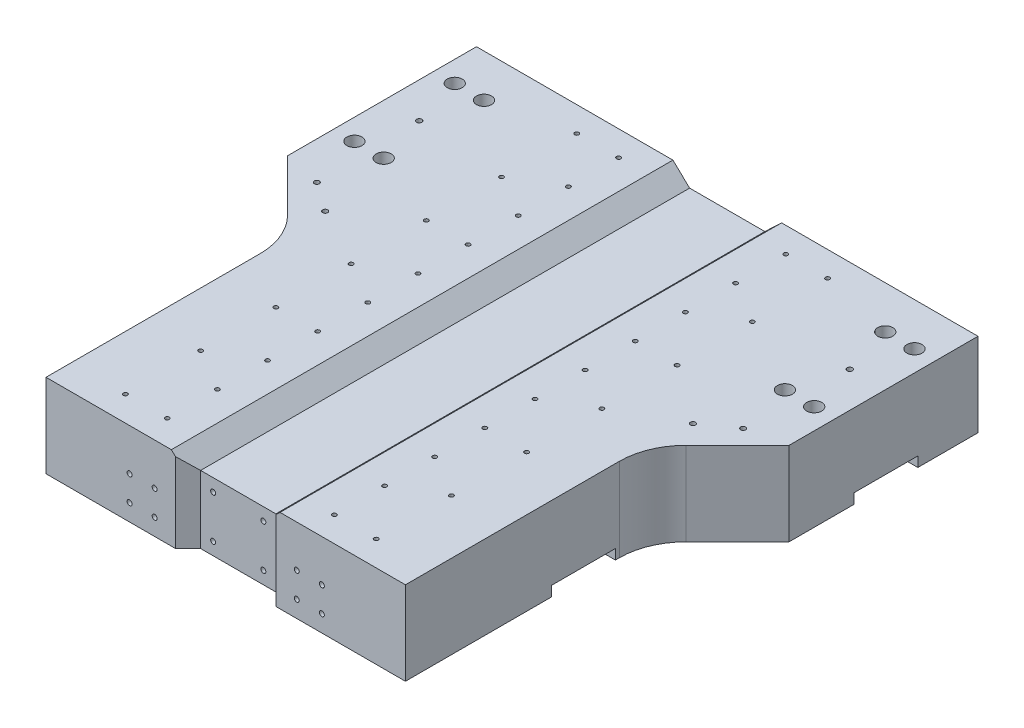
SolidWorks part; units mm, degrees
ref_plane "Front Plane" through (0, 0, 0) normal (0, 0, 1) x (1, 0, 0)
ref_plane "Top Plane" through (0, 0, 0) normal (0, 1, 0) x (1, 0, 0)
ref_plane "Right Plane" through (0, 0, 0) normal (1, 0, 0) x (0, 0, -1)
sketch "Sketch1" plane through (0, 0, 0) normal (0, 1, 0) x (1, 0, 0)
  line L1 (-300, 300) -> (300, 300)
  line L2 (-300, 300) -> (-300, -300)
  line L3 (-300, -300) -> (300, -300)
  line L4 (300, 300) -> (300, -300)
  line L5 (0, -300) -> (0, 300) construction
  line L6 (-300, 0) -> (300, 0) construction
  point P0 (0, 0)
  dimension "D1" = 600
extrude "Boss-Extrude1" add sketch "Sketch1" along normal blind 100
sketch "Sketch2" plane through (0, 100, 0) normal (0, 1, 0) x (1, 0, 0)
  line L0 (-300, -300) -> (-220, -300)
  line L9 (-300, -300) -> (300, -300) construction
  line L11 (300, -300) -> (220, -300)
  line L13 (-300, 300) -> (-300, -300) construction
  line L15 (-300, -300) -> (-300, 60)
  line L16 (300, -300) -> (300, 60)
  line L38 (-300, 60) -> (-300, 74)
  line L41 (300, 60) -> (300, 74)
  line L45 (-220, 74) -> (-300, 74)
  line L48 (220, 74) -> (300, 74)
  line L49 (-220, 74) -> (-215, 74)
  line L50 (-215, 74) -> (-215, -300)
  line L51 (-215, -300) -> (-220, -300)
  line L52 (220, 74) -> (215, 74)
  line L53 (215, 74) -> (215, -300)
  line L54 (215, -300) -> (220, -300)
extrude "Cut-Extrude1" cut sketch "Sketch2" against normal through all
chamfer "Chamfer5" distance 85 angle 45 2 edges at (-215, 50, -74) (215, 50, -74)
sketch "Sketch3" plane through (0, 0, 300) normal (0, 0, 1) x (1, 0, 0)
  line L0 (-35, 81) -> (-45, 81)
  line L2 (35, 81) -> (45, 81)
  line L4 (0, 81) -> (35, 81)
  line L8 (0, 81) -> (-35, 81)
  line L10 (-45, 100) -> (45, 100)
  line L13 (-215, 100) -> (215, 100) construction
  line L14 (-65, 100) -> (-45, 100)
  line L17 (45, 100) -> (65, 100)
  line L22 (-45, 81) -> (-65, 100)
  line L23 (45, 81) -> (65, 100)
extrude "Cut-Extrude2" cut sketch "Sketch3" against normal through all
sketch "Sketch9" plane through (0, 100, 0) normal (0, 1, 0) x (1, 0, 0)
  circle A0 centre (275, 129) radius 9.017
  circle A1 centre (240, 129) radius 9.017
  circle A3 centre (240, 249) radius 9.017
  circle A5 centre (275, 249) radius 9.017
  circle A6 centre (-275, 129) radius 9.017
  circle A7 centre (-240, 249) radius 9.017
  circle A8 centre (-275, 249) radius 9.017
  circle A11 centre (-240, 129) radius 9.017
  circle A12 centre (240, 189) radius 9.017 [skipped]
  circle A13 centre (275, 189) radius 9.017 [skipped]
  dimension "D1" = 2
  dimension "D2" = 3
extrude "Cut-Extrude5" cut sketch "Sketch9" against normal through all
sketch "Sketch12" plane through (0, 100, 0) normal (0, 1, 0) x (1, 0, 0)
  circle A40 centre (-100, -270) radius 2.5
  circle A41 centre (100, -270) radius 2.5
  circle A42 centre (100, -210) radius 2.5
  circle A43 centre (100, -150) radius 2.5
  circle A44 centre (100, -90) radius 2.5
  circle A45 centre (100, -30) radius 2.5
  circle A46 centre (100, 30) radius 2.5
  circle A47 centre (100, 90) radius 2.5
  circle A48 centre (100, 150) radius 2.5
  circle A49 centre (100, 210) radius 2.5
  circle A50 centre (100, 270) radius 2.5
  circle A61 centre (-100, -210) radius 2.5
  circle A62 centre (-100, -150) radius 2.5
  circle A63 centre (-100, -90) radius 2.5
  circle A64 centre (-100, -30) radius 2.5
  circle A65 centre (-100, 30) radius 2.5
  circle A66 centre (-100, 90) radius 2.5
  circle A67 centre (-100, 150) radius 2.5
  circle A68 centre (-100, 210) radius 2.5
  circle A69 centre (-100, 270) radius 2.5
  dimension "D1" = 2
  dimension "D2" = 10
extrude "Cut-Extrude7" cut sketch "Sketch12" against normal blind 30
sketch "Sketch14" plane through (0, 81, 0) normal (0, 1, 0) x (1, 0, 0)
  line L5 (-45, -300) -> (45, -300)
  line L6 (-45, -300) -> (-45, -285)
  line L11 (45, -285) -> (45, -300)
  line L15 (-45, -285) -> (45, -285)
extrude "Cut-Extrude8" cut sketch "Sketch14" against normal through all
chamfer "Chamfer3" distance 15 angle 45 2 edges at (45, 40.5, 300) (-45, 40.5, 300)
sketch "Sketch15" plane through (-300, 0, 0) normal (-1, 0, 0) x (0, 0, 1)
  line L0 (125, -0.7) -> (125, 12) construction
  line L1 (125, 12) -> (48.8, 12) construction
  line L2 (48.8, 12) -> (48.8, -0.7) construction
  line L3 (48.8, -0.7) -> (125, -0.7) construction
  line L4 (-228, 12) -> (-228, -0.7) construction
  line L5 (-228, -0.7) -> (-151.8, -0.7) construction
  line L6 (-151.8, -0.7) -> (-151.8, 12) construction
  line L7 (-151.8, 12) -> (-228, 12) construction
  line L8 (125, -0.7) -> (125, 12)
  line L9 (125, 12) -> (48.8, 12)
  line L10 (48.8, 12) -> (48.8, -0.7)
  line L11 (48.8, -0.7) -> (125, -0.7)
  line L12 (-228, 12) -> (-228, -0.7)
  line L13 (-228, -0.7) -> (-151.8, -0.7)
  line L14 (-151.8, -0.7) -> (-151.8, 12)
  line L15 (-151.8, 12) -> (-228, 12)
extrude "Cut-Extrude9" cut sketch "Sketch15" against normal through all
sketch "Sketch22" plane through (0, 0, -300) normal (0, 0, -1) x (-1, 0, 0)
  line L0 (-45, 81) -> (-45, 0)
  line L1 (-300, 0) -> (300, 0) construction
  line L2 (-45, 0) -> (45, 0)
  line L3 (45, 0) -> (45, 81)
  line L4 (45, 81) -> (-45, 81)
sketch "Sketch17" plane through (0, 0, 285) normal (0, 0, 1) x (1, 0, 0)
  line L8 (30, 66) -> (-30, 66)
  line L9 (-30, 66) -> (-30, 15)
  line L10 (-30, 15) -> (30, 15)
  line L11 (30, 15) -> (30, 66)
  line L12 (30, 66) -> (-30, 66)
  line L13 (-30, 66) -> (-30, 15)
  line L14 (-30, 15) -> (30, 15)
  line L15 (30, 15) -> (30, 66)
  dimension "D1" = 15
sketch "Sketch19" plane through (0, 0, -300) normal (0, 0, -1) x (-1, 0, 0)
  line L0 (30, 66) -> (30, 15) construction
  line L1 (30, 15) -> (-30, 15) construction
  line L2 (-30, 15) -> (-30, 66) construction
  line L3 (-30, 66) -> (30, 66) construction
  line L4 (30, 66) -> (30, 15)
  line L5 (30, 15) -> (-30, 15)
  line L6 (-30, 15) -> (-30, 66)
  line L7 (-30, 66) -> (30, 66)
sketch "Sketch20" plane through (0, 0, 300) normal (0, 0, 1) x (1, 0, 0)
  line L2 (85, 100) -> (85, 50)
  line L3 (-85, 0) -> (-85, 20)
  line L4 (-215, 100) -> (-65, 100) construction
  line L5 (-85, 100) -> (-85, 50)
  line L6 (115, 100) -> (115, 50)
  line L7 (-115, 100) -> (-115, 50)
  line L8 (0, 34.1921) -> (0, 91.6213)
  line L9 (-215, 0) -> (-60, 0) construction
  line L10 (-115, 0) -> (-115, 20)
  line L11 (85, 0) -> (85, 20)
  line L12 (115, 0) -> (115, 20)
sketch "Sketch21" plane through (0, 0, -300) normal (0, 0, -1) x (-1, 0, 0)
  line L4 (-115, 100) -> (-115, 80)
  line L5 (-85, 100) -> (-85, 80)
  line L6 (85, 100) -> (85, 80)
  line L7 (115, 100) -> (115, 80)
  line L8 (115, 0) -> (115, 20) construction
  line L9 (85, 0) -> (85, 20) construction
  line L10 (-85, 0) -> (-85, 20) construction
  line L11 (-115, 0) -> (-115, 20) construction
  line L12 (115, 0) -> (115, 20)
  line L13 (85, 0) -> (85, 20)
  line L14 (-85, 0) -> (-85, 20)
  line L15 (-115, 0) -> (-115, 20)
hole_wizard "Ø6.0mm Dowel Hole1" positions "3DSketch2" profile "Sketch18" hole size "Ø6.0" standard "ANSI Metric"
sketch3d "3DSketch2"
  point P0 (-30, 66, 285)
  point P3 (30, 66, 285)
  point P6 (30, 15, 285)
  point P9 (-30, 15, 285)
  point P13 (30, 66, -300)
  point P16 (-30, 66, -300)
  point P19 (-30, 15, -300)
  point P22 (30, 15, -300)
  point P26 (-85, 50, 300)
  point P29 (-115, 50, 300)
  point P32 (85, 50, 300)
  point P35 (115, 50, 300)
  point P38 (-115, 80, -300)
  point P41 (-85, 80, -300)
  point P44 (85, 80, -300)
  point P47 (115, 80, -300)
  point P50 (-115, 20, 300)
  point P53 (-85, 20, 300)
  point P56 (85, 20, 300)
  point P59 (115, 20, 300)
  point P62 (-115, 20, -300)
  point P65 (-85, 20, -300)
  point P68 (85, 20, -300)
  point P71 (115, 20, -300)
sketch "Sketch18" plane through (-30, 66, 285) normal (1, 0, 0) x (0, -1, 0)
  line L0 (0, 0) -> (0, 31.8026)
  line L1 (0, 31.8026) -> (3, 30)
  line L2 (3, 30) -> (3, 0)
  line L5 (3, 0) -> (0, 0)
  line L10 (0, 31.8026) -> (-3, 30) construction
  line L11 (0, -6.35) -> (0, 107.95) construction
  dimension "Hole Dia." = 6
  dimension "Hole Depth" = 30
  dimension "Drill Angle" = 118
sketch "Sketch23" plane through (0, 100, 0) normal (0, 1, 0) x (1, 0, 0)
  circle A0 centre (-257.5, 189) radius 3.175
  circle A1 centre (257.5, 189) radius 3.175
extrude "Cut-Extrude10" cut sketch "Sketch23" against normal through all
sketch "Sketch24" plane through (0, 100, 0) normal (0, 1, 0) x (1, 0, 0)
  line L0 (210, 74) -> (300, 74) construction
  line L1 (210, 74) -> (300, 74)
  line L2 (210, 74) -> (210, 4)
  line L3 (210, 39) -> (220, 39)
  line L4 (255, 74) -> (255, 64)
  line L5 (0, 0) -> (0, -82.778)
  circle A0 centre (255, 64) radius 3
  circle A1 centre (220, 39) radius 3
  circle A2 centre (-220, 39) radius 3
  circle A3 centre (-255, 64) radius 3
extrude "Cut-Extrude11" cut sketch "Sketch24" against normal blind 20 contours A3 | A2 | A0 | A1
fillet "Fillet1" radius 80 2 edges at (215, 50, 11) (-215, 50, 11)
sketch "Sketch25" plane through (0, 100, 0) normal (0, 1, 0) x (1, 0, 0)
  line L0 (0, 0) -> (0, -72.5445)
  circle A4 centre (150, 270) radius 2.5
  circle A5 centre (150, 90) radius 2.5
  circle A6 centre (150, -90) radius 2.5
  circle A7 centre (150, -270) radius 2.5
  circle A8 centre (-150, -270) radius 2.5
  circle A9 centre (-150, -90) radius 2.5
  circle A10 centre (-150, 90) radius 2.5
  circle A11 centre (-150, 270) radius 2.5
  circle A12 centre (-150, 180) radius 2.5
  circle A13 centre (150, 180) radius 2.5
  circle A14 centre (150, 0) radius 2.5
  circle A15 centre (-150, 0) radius 2.5
  circle A16 centre (150, -180) radius 2.5
  circle A17 centre (-150, -180) radius 2.5
hole_wizard "Ø5.0mm Dowel Hole1" positions "Sketch26" profile "Sketch27" hole size "Ø5.0" standard "ANSI Metric"
sketch "Sketch26" plane through (0, 100, 0) normal (0, 1, 0) x (1, 0, 0)
  point P0 (-150, 270)
  point P3 (150, 270)
  point P6 (-150, 90)
  point P9 (150, 90)
  point P12 (-150, -90)
  point P15 (150, -90)
  point P18 (-150, -270)
  point P21 (150, -270)
  point P25 (150, 180)
  point P28 (-150, 180)
  point P31 (-150, 0)
  point P34 (150, 0)
  point P37 (150, -180)
  point P40 (-150, -180)
sketch "Sketch27" plane through (-150, 100, -270) normal (1, 0, 0) x (0, 0, 1)
  line L0 (0, 0) -> (0, 30)
  line L1 (0, 30) -> (2.5, 28.4978)
  line L2 (2.5, 28.4978) -> (2.5, 0)
  line L5 (2.5, 0) -> (0, 0)
  line L10 (0, 30) -> (-2.5, 28.4978) construction
  line L11 (0, -6.35) -> (0, 107.95) construction
  dimension "Hole Dia." = 5
  dimension "Hole Depth" = 30
  dimension "Drill Angle" = 118
